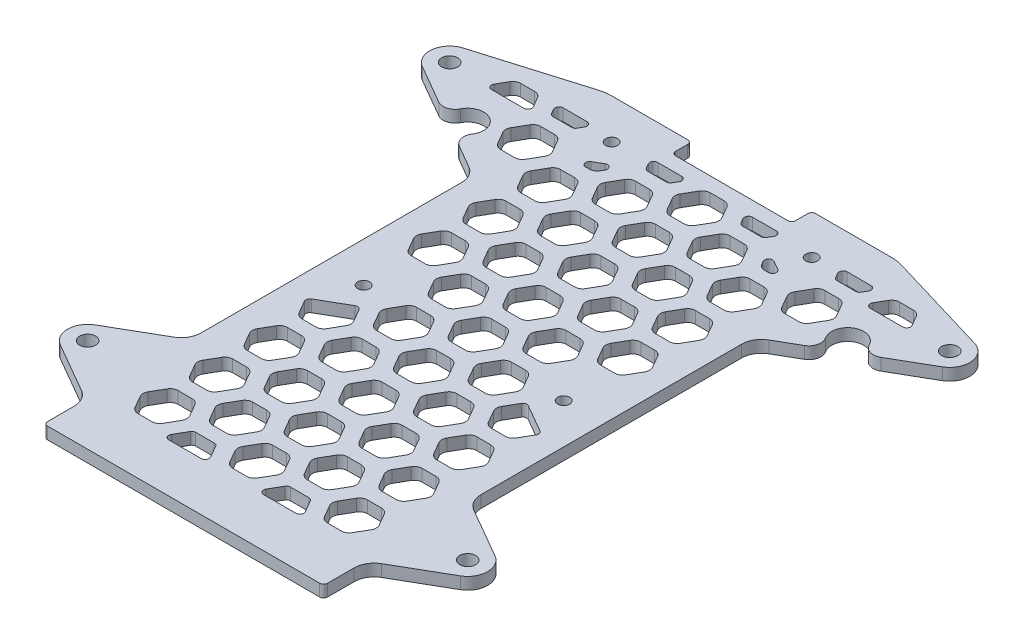
SolidWorks part; units mm, degrees
material "Thornel Mat VMA"
ref_plane "前视基准面" through (0, 0, 0) normal (0, 0, 1) x (1, 0, 0)
ref_plane "上视基准面" through (0, 0, 0) normal (0, 1, 0) x (1, 0, 0)
ref_plane "右视基准面" through (0, 0, 0) normal (1, 0, 0) x (0, 0, -1)
sketch "草图2" plane through (0, 0, 0) normal (0, 1, 0) x (1, 0, 0)
  line L0 (-43.1514, -19.9444) -> (-37.5, -23.2073)
  line L1 (35, -124.3771) -> (35, -132)
  line L3 (-47.5, -108.5) -> (-47.5, -13.5) construction
  line L6 (-37.8634, 9.5813) -> (-63.9317, 1.7906)
  line L7 (50, -112.8301) -> (37.5, -120.047)
  line L8 (37.5, -96.953) -> (50, -104.1699)
  line L11 (35, -27.5374) -> (35, -92.6229)
  line L14 (0, -55) -> (0, 55) construction
  line L16 (-35, 10) -> (35, 10)
  line L20 (43.1514, -19.9444) -> (37.5, -23.2073)
  line L23 (65, -7.3301) -> (55.2553, -12.9562)
  line L25 (-25, 0) -> (25, 0) construction
  line L26 (-25, 0) -> (-25, -62) construction
  line L27 (-25, -62) -> (25, -62) construction
  line L28 (25, 0) -> (25, -62) construction
  line L29 (-35, -124.3771) -> (-35, -132)
  line L30 (-35, -132) -> (35, -132)
  line L32 (-65, -7.3301) -> (-55.2553, -12.9562)
  line L33 (-35, -27.5374) -> (-35, -92.6229)
  line L34 (-37.5, -96.953) -> (-50, -104.1699)
  line L35 (-50, -112.8301) -> (-37.5, -120.047)
  line L36 (37.8634, 9.5813) -> (63.9317, 1.7906)
  arc A10 (-44.158, -15.6979) -> (-51.0745, -11.7047) centre (-47.5, -13.5) ccw
  circle A45 centre (-25, 0) radius 1.5
  circle A46 centre (-47.5, -38.5) radius 4 construction
  circle A47 centre (-62.5, -3) radius 2
  circle A49 centre (62.5, -3) radius 2
  circle A51 centre (47.5, -38.5) radius 4 construction
  circle A52 centre (25, 0) radius 1.5
  circle A53 centre (-25, -62) radius 1.5
  circle A54 centre (25, -62) radius 1.5
  arc A58 (-35, 10) -> (-37.8634, 9.5813) centre (-35, 0) ccw
  circle A59 centre (-47.5, -108.5) radius 2
  arc A60 (-50, -104.1699) -> (-50, -112.8301) centre (-47.5, -108.5) ccw
  arc A61 (-63.9317, 1.7906) -> (-65, -7.3301) centre (-62.5, -3) ccw
  arc A62 (-43.1514, -19.9444) -> (-44.158, -15.6979) centre (-41.6514, -17.3463) cw
  arc A63 (-51.0745, -11.7047) -> (-55.2553, -12.9562) centre (-53.7553, -10.3582) cw
  arc A64 (-35, -124.3771) -> (-37.5, -120.047) centre (-40, -124.3771) ccw
  arc A65 (-35, -92.6229) -> (-37.5, -96.953) centre (-40, -92.6229) cw
  arc A66 (-37.5, -23.2073) -> (-35, -27.5374) centre (-40, -27.5374) cw
  arc A67 (35, -124.3771) -> (37.5, -120.047) centre (40, -124.3771) cw
  circle A68 centre (47.5, -108.5) radius 2
  arc A69 (50, -104.1699) -> (50, -112.8301) centre (47.5, -108.5) cw
  arc A70 (35, -92.6229) -> (37.5, -96.953) centre (40, -92.6229) ccw
  arc A71 (37.5, -23.2073) -> (35, -27.5374) centre (40, -27.5374) ccw
  arc A72 (43.1514, -19.9444) -> (44.158, -15.6979) centre (41.6514, -17.3463) ccw
  arc A73 (44.158, -15.6979) -> (51.0745, -11.7047) centre (47.5, -13.5) cw
  arc A74 (51.0745, -11.7047) -> (55.2553, -12.9562) centre (53.7553, -10.3582) ccw
  arc A75 (63.9317, 1.7906) -> (65, -7.3301) centre (62.5, -3) cw
  arc A76 (35, 10) -> (37.8634, 9.5813) centre (35, 0) cw
  dimension "D3" = 10
  dimension "D4" = 25
  dimension "D7" = 5
  dimension "D8" = 125
  dimension "D9" = 13
  dimension "D10" = 3
  dimension "D11" = 10
  dimension "D6" = 4
  dimension "D19" = 120
  dimension "D20" = 3
  dimension "D21" = 62
  dimension "D22" = 50
  dimension "D23" = 5
  dimension "D13" = 15
  dimension "D14" = 10.5
  dimension "D12" = 70
  dimension "D15" = 10
  dimension "D16" = 70
  dimension "D17" = 120
  dimension "D18" = 120
  dimension "D5" = 8
extrude "凸台-拉伸1" add sketch "草图2" along normal blind 3
sketch "草图5" plane through (0, 3, 0) normal (0, 1, 0) x (1, 0, 0)
  line L0 (2.8868, -8.6667) -> (2.8868, -12.3333) construction
  line L26 (-20.7846, -12.3333) -> (-26.5581, -12.3333)
  line L29 (-26.5581, -12.3333) -> (-29.4449, -17.3333)
  line L34 (-29.4449, -17.3333) -> (-26.5581, -22.3333)
  line L35 (-26.5581, -22.3333) -> (-20.7846, -22.3333)
  line L47 (35, 10) -> (-35, 10) construction
  line L60 (-20.7846, -22.3333) -> (-17.8979, -17.3333)
  line L61 (-17.8979, -17.3333) -> (-20.7846, -12.3333)
  line L104 (0, 0) -> (0, 10) construction
  line L105 (-25, 0) -> (25, -62) construction
  line L109 (-11.8357, -10.5) -> (-11.8357, -24.1667) construction
  line L113 (-15, 10) -> (15, 10)
  line L114 (-15, 10) -> (-15, 5)
  line L115 (-15, 5) -> (15, 5)
  line L116 (15, 10) -> (15, 5)
  line L122 (2.8868, -12.3333) -> (-2.8868, -12.3333)
  line L123 (-2.8868, -12.3333) -> (-5.7735, -17.3333)
  line L124 (-5.7735, -17.3333) -> (-2.8868, -22.3333)
  line L125 (-2.8868, -22.3333) -> (2.8868, -22.3333)
  line L126 (2.8868, -22.3333) -> (5.7735, -17.3333)
  line L127 (5.7735, -17.3333) -> (2.8868, -12.3333)
  line L128 (-8.9489, -19.1667) -> (-14.7224, -19.1667)
  line L129 (-14.7224, -19.1667) -> (-17.6092, -24.1667)
  line L130 (-17.6092, -24.1667) -> (-14.7224, -29.1667)
  line L131 (-14.7224, -29.1667) -> (-8.9489, -29.1667)
  line L132 (-8.9489, -29.1667) -> (-6.0622, -24.1667)
  line L133 (-6.0622, -24.1667) -> (-8.9489, -19.1667)
  line L134 (-8.9489, -5.5) -> (-14.7224, -5.5)
  line L135 (-14.7224, -5.5) -> (-17.6092, -10.5)
  line L136 (-17.6092, -10.5) -> (-14.7224, -15.5)
  line L137 (-14.7224, -15.5) -> (-8.9489, -15.5)
  line L138 (-8.9489, -15.5) -> (-6.0622, -10.5)
  line L139 (-6.0622, -10.5) -> (-8.9489, -5.5)
  line L140 (-11.8357, -24.1667) -> (0, -31) construction
  line L141 (0, -31) -> (0, -17.3333) construction
  line L142 (0, -17.3333) -> (-11.8357, -24.1667) construction
  line L143 (0, -3.6667) -> (0, -17.3333) construction
  line L144 (2.8868, 1.3333) -> (-2.8868, 1.3333)
  line L145 (-2.8868, 1.3333) -> (-5.7735, -3.6667)
  line L146 (-5.7735, -3.6667) -> (-2.8868, -8.6667)
  line L147 (-2.8868, -8.6667) -> (2.8868, -8.6667)
  line L148 (2.8868, -8.6667) -> (5.7735, -3.6667)
  line L149 (5.7735, -3.6667) -> (2.8868, 1.3333)
  line L151 (2.8868, 1.3333) -> (2.8868, 5) construction
  line L155 (-32.6203, -5.5) -> (-38.3938, -5.5)
  line L156 (-38.3938, -5.5) -> (-41.2805, -10.5)
  line L157 (-41.2805, -10.5) -> (-38.3938, -15.5)
  line L158 (-38.3938, -15.5) -> (-32.6203, -15.5)
  line L159 (-32.6203, -15.5) -> (-29.7335, -10.5)
  line L160 (-29.7335, -10.5) -> (-32.6203, -5.5)
  line L164 (-26.5581, -8.6667) -> (-20.7846, -8.6667)
  line L165 (-20.7846, -8.6667) -> (-17.8979, -3.6667)
  line L185 (-44.456, 1.3333) -> (-50.2295, 1.3333)
  line L186 (-50.2295, 1.3333) -> (-53.1162, -3.6667)
  line L190 (-41.5692, -3.6667) -> (-44.456, 1.3333)
  line L191 (-20.7846, -39.6667) -> (-26.5581, -39.6667)
  line L192 (-26.5581, -39.6667) -> (-29.4449, -44.6667)
  line L193 (-29.4449, -44.6667) -> (-26.5581, -49.6667)
  line L194 (-26.5581, -49.6667) -> (-20.7846, -49.6667)
  line L195 (-20.7846, -49.6667) -> (-17.8979, -44.6667)
  line L196 (-17.8979, -44.6667) -> (-20.7846, -39.6667)
  line L209 (-20.7846, -26) -> (-26.5581, -26)
  line L210 (-26.5581, -26) -> (-29.4449, -31)
  line L211 (-29.4449, -31) -> (-26.5581, -36)
  line L212 (-26.5581, -36) -> (-20.7846, -36)
  line L213 (-20.7846, -36) -> (-17.8979, -31)
  line L214 (-17.8979, -31) -> (-20.7846, -26)
  line L241 (-29.4449, -72) -> (-26.5581, -77)
  line L242 (-26.5581, -77) -> (-20.7846, -77)
  line L243 (-20.7846, -77) -> (-17.8979, -72)
  line L244 (-17.8979, -72) -> (-20.7846, -67)
  line L287 (-20.7846, -94.3333) -> (-26.5581, -94.3333)
  line L288 (-26.5581, -94.3333) -> (-29.4449, -99.3333)
  line L289 (-29.4449, -99.3333) -> (-26.5581, -104.3333)
  line L290 (-26.5581, -104.3333) -> (-20.7846, -104.3333)
  line L291 (-20.7846, -104.3333) -> (-17.8979, -99.3333)
  line L292 (-17.8979, -99.3333) -> (-20.7846, -94.3333)
  line L305 (-20.7846, -80.6667) -> (-26.5581, -80.6667)
  line L306 (-26.5581, -80.6667) -> (-29.4449, -85.6667)
  line L307 (-29.4449, -85.6667) -> (-26.5581, -90.6667)
  line L308 (-26.5581, -90.6667) -> (-20.7846, -90.6667)
  line L309 (-20.7846, -90.6667) -> (-17.8979, -85.6667)
  line L310 (-17.8979, -85.6667) -> (-20.7846, -80.6667)
  line L353 (-20.7846, -108) -> (-26.5581, -108)
  line L354 (-26.5581, -108) -> (-29.4449, -113)
  line L355 (-29.4449, -113) -> (-26.5581, -118)
  line L356 (-26.5581, -118) -> (-20.7846, -118)
  line L357 (-20.7846, -118) -> (-17.8979, -113)
  line L358 (-17.8979, -113) -> (-20.7846, -108)
  line L431 (2.8868, -39.6667) -> (-2.8868, -39.6667)
  line L432 (-2.8868, -39.6667) -> (-5.7735, -44.6667)
  line L433 (-5.7735, -44.6667) -> (-2.8868, -49.6667)
  line L434 (-2.8868, -49.6667) -> (2.8868, -49.6667)
  line L435 (2.8868, -49.6667) -> (5.7735, -44.6667)
  line L436 (5.7735, -44.6667) -> (2.8868, -39.6667)
  line L437 (-8.9489, -46.5) -> (-14.7224, -46.5)
  line L438 (-14.7224, -46.5) -> (-17.6092, -51.5)
  line L439 (-17.6092, -51.5) -> (-14.7224, -56.5)
  line L440 (-14.7224, -56.5) -> (-8.9489, -56.5)
  line L441 (-8.9489, -56.5) -> (-6.0622, -51.5)
  line L442 (-6.0622, -51.5) -> (-8.9489, -46.5)
  line L443 (-8.9489, -32.8333) -> (-14.7224, -32.8333)
  line L444 (-14.7224, -32.8333) -> (-17.6092, -37.8333)
  line L445 (-17.6092, -37.8333) -> (-14.7224, -42.8333)
  line L446 (-14.7224, -42.8333) -> (-8.9489, -42.8333)
  line L447 (-8.9489, -42.8333) -> (-6.0622, -37.8333)
  line L448 (-6.0622, -37.8333) -> (-8.9489, -32.8333)
  line L449 (2.8868, -26) -> (-2.8868, -26)
  line L450 (-2.8868, -26) -> (-5.7735, -31)
  line L451 (-5.7735, -31) -> (-2.8868, -36)
  line L452 (-2.8868, -36) -> (2.8868, -36)
  line L453 (2.8868, -36) -> (5.7735, -31)
  line L454 (5.7735, -31) -> (2.8868, -26)
  line L455 (2.8868, -67) -> (-2.8868, -67)
  line L456 (-2.8868, -67) -> (-5.7735, -72)
  line L457 (-5.7735, -72) -> (-2.8868, -77)
  line L458 (-2.8868, -77) -> (2.8868, -77)
  line L459 (2.8868, -77) -> (5.7735, -72)
  line L460 (5.7735, -72) -> (2.8868, -67)
  line L461 (-8.9489, -73.8333) -> (-14.7224, -73.8333)
  line L462 (-14.7224, -73.8333) -> (-17.6092, -78.8333)
  line L463 (-17.6092, -78.8333) -> (-14.7224, -83.8333)
  line L464 (-14.7224, -83.8333) -> (-8.9489, -83.8333)
  line L465 (-8.9489, -83.8333) -> (-6.0622, -78.8333)
  line L466 (-6.0622, -78.8333) -> (-8.9489, -73.8333)
  line L467 (-8.9489, -60.1667) -> (-14.7224, -60.1667)
  line L468 (-14.7224, -60.1667) -> (-17.6092, -65.1667)
  line L469 (-17.6092, -65.1667) -> (-14.7224, -70.1667)
  line L470 (-14.7224, -70.1667) -> (-8.9489, -70.1667)
  line L471 (-8.9489, -70.1667) -> (-6.0622, -65.1667)
  line L472 (-6.0622, -65.1667) -> (-8.9489, -60.1667)
  line L473 (2.8868, -53.3333) -> (-2.8868, -53.3333)
  line L474 (-2.8868, -53.3333) -> (-5.7735, -58.3333)
  line L475 (-5.7735, -58.3333) -> (-2.8868, -63.3333)
  line L476 (-2.8868, -63.3333) -> (2.8868, -63.3333)
  line L477 (2.8868, -63.3333) -> (5.7735, -58.3333)
  line L478 (5.7735, -58.3333) -> (2.8868, -53.3333)
  line L479 (2.8868, -94.3333) -> (-2.8868, -94.3333)
  line L480 (-2.8868, -94.3333) -> (-5.7735, -99.3333)
  line L481 (-5.7735, -99.3333) -> (-2.8868, -104.3333)
  line L482 (-2.8868, -104.3333) -> (2.8868, -104.3333)
  line L483 (2.8868, -104.3333) -> (5.7735, -99.3333)
  line L484 (5.7735, -99.3333) -> (2.8868, -94.3333)
  line L485 (-8.9489, -101.1667) -> (-14.7224, -101.1667)
  line L486 (-14.7224, -101.1667) -> (-17.6092, -106.1667)
  line L487 (-17.6092, -106.1667) -> (-14.7224, -111.1667)
  line L488 (-14.7224, -111.1667) -> (-8.9489, -111.1667)
  line L489 (-8.9489, -111.1667) -> (-6.0622, -106.1667)
  line L490 (-6.0622, -106.1667) -> (-8.9489, -101.1667)
  line L491 (-8.9489, -87.5) -> (-14.7224, -87.5)
  line L492 (-14.7224, -87.5) -> (-17.6092, -92.5)
  line L493 (-17.6092, -92.5) -> (-14.7224, -97.5)
  line L494 (-14.7224, -97.5) -> (-8.9489, -97.5)
  line L495 (-8.9489, -97.5) -> (-6.0622, -92.5)
  line L496 (-6.0622, -92.5) -> (-8.9489, -87.5)
  line L497 (2.8868, -80.6667) -> (-2.8868, -80.6667)
  line L498 (-2.8868, -80.6667) -> (-5.7735, -85.6667)
  line L499 (-5.7735, -85.6667) -> (-2.8868, -90.6667)
  line L500 (-2.8868, -90.6667) -> (2.8868, -90.6667)
  line L501 (2.8868, -90.6667) -> (5.7735, -85.6667)
  line L502 (5.7735, -85.6667) -> (2.8868, -80.6667)
  line L515 (-8.9489, -114.8333) -> (-14.7224, -114.8333)
  line L516 (-14.7224, -114.8333) -> (-17.6092, -119.8333)
  line L520 (-6.0622, -119.8333) -> (-8.9489, -114.8333)
  line L521 (2.8868, -108) -> (-2.8868, -108)
  line L522 (-2.8868, -108) -> (-5.7735, -113)
  line L523 (-5.7735, -113) -> (-2.8868, -118)
  line L524 (-2.8868, -118) -> (2.8868, -118)
  line L525 (2.8868, -118) -> (5.7735, -113)
  line L526 (5.7735, -113) -> (2.8868, -108)
  line L551 (-11.8357, -10.5) -> (-23.6714, -17.3333) construction
  line L552 (-23.6714, -17.3333) -> (-11.8357, -24.1667) construction
  line L553 (-17.8979, -3.6667) -> (-26.5581, -8.6667)
  line L554 (-62.0652, -56.5) -> (-56.2917, -56.5) [skipped]
  line L555 (-44.456, -67) -> (-50.2295, -67) [skipped]
  line L556 (-50.2295, -67) -> (-53.1162, -72) [skipped]
  line L557 (-53.1162, -72) -> (-50.2295, -77) [skipped]
  line L558 (-50.2295, -77) -> (-44.456, -77) [skipped]
  line L559 (-44.456, -77) -> (-41.5692, -72) [skipped]
  line L560 (-41.5692, -72) -> (-44.456, -67) [skipped]
  line L561 (-56.2917, -73.8333) -> (-62.0652, -73.8333) [skipped]
  line L562 (-62.0652, -73.8333) -> (-64.9519, -78.8333) [skipped]
  line L563 (-64.9519, -78.8333) -> (-62.0652, -83.8333) [skipped]
  line L564 (-62.0652, -83.8333) -> (-56.2917, -83.8333) [skipped]
  line L565 (-56.2917, -83.8333) -> (-53.4049, -78.8333) [skipped]
  line L566 (-53.4049, -78.8333) -> (-56.2917, -73.8333) [skipped]
  line L567 (-56.2917, -60.1667) -> (-62.0652, -60.1667) [skipped]
  line L568 (-62.0652, -60.1667) -> (-64.9519, -65.1667) [skipped]
  line L569 (-64.9519, -65.1667) -> (-62.0652, -70.1667) [skipped]
  line L570 (-62.0652, -70.1667) -> (-56.2917, -70.1667) [skipped]
  line L571 (-56.2917, -70.1667) -> (-53.4049, -65.1667) [skipped]
  line L572 (-53.4049, -65.1667) -> (-56.2917, -60.1667) [skipped]
  line L573 (-53.1162, -58.3333) -> (-50.2295, -63.3333) [skipped]
  line L574 (-50.2295, -63.3333) -> (-44.456, -63.3333) [skipped]
  line L575 (-44.456, -63.3333) -> (-41.5692, -58.3333) [skipped]
  line L576 (-44.456, -94.3333) -> (-50.2295, -94.3333) [skipped]
  line L577 (-50.2295, -94.3333) -> (-53.1162, -99.3333) [skipped]
  line L578 (-53.1162, -99.3333) -> (-50.2295, -104.3333) [skipped]
  line L579 (-50.2295, -104.3333) -> (-44.456, -104.3333) [skipped]
  line L580 (-44.456, -104.3333) -> (-41.5692, -99.3333) [skipped]
  line L581 (-41.5692, -99.3333) -> (-44.456, -94.3333) [skipped]
  line L582 (-56.2917, -101.1667) -> (-62.0652, -101.1667) [skipped]
  line L583 (-62.0652, -101.1667) -> (-64.9519, -106.1667) [skipped]
  line L584 (-64.9519, -106.1667) -> (-62.0652, -111.1667) [skipped]
  line L585 (-62.0652, -111.1667) -> (-56.2917, -111.1667) [skipped]
  line L586 (-56.2917, -111.1667) -> (-53.4049, -106.1667) [skipped]
  line L587 (-53.4049, -106.1667) -> (-56.2917, -101.1667) [skipped]
  line L588 (-56.2917, -87.5) -> (-62.0652, -87.5) [skipped]
  line L589 (-62.0652, -87.5) -> (-64.9519, -92.5) [skipped]
  line L590 (-64.9519, -92.5) -> (-62.0652, -97.5) [skipped]
  line L591 (-62.0652, -97.5) -> (-56.2917, -97.5) [skipped]
  line L592 (-56.2917, -97.5) -> (-53.4049, -92.5) [skipped]
  line L593 (-53.4049, -92.5) -> (-56.2917, -87.5) [skipped]
  line L594 (-44.456, -80.6667) -> (-50.2295, -80.6667) [skipped]
  line L595 (-50.2295, -80.6667) -> (-53.1162, -85.6667) [skipped]
  line L596 (-53.1162, -85.6667) -> (-50.2295, -90.6667) [skipped]
  line L597 (-50.2295, -90.6667) -> (-44.456, -90.6667) [skipped]
  line L598 (-44.456, -90.6667) -> (-41.5692, -85.6667) [skipped]
  line L599 (-41.5692, -85.6667) -> (-44.456, -80.6667) [skipped]
  line L600 (-44.456, -121.6667) -> (-50.2295, -121.6667) [skipped]
  line L601 (-50.2295, -121.6667) -> (-53.1162, -126.6667) [skipped]
  line L602 (-53.1162, -126.6667) -> (-50.2295, -131.6667) [skipped]
  line L603 (-50.2295, -131.6667) -> (-44.456, -131.6667) [skipped]
  line L604 (-44.456, -131.6667) -> (-41.5692, -126.6667) [skipped]
  line L605 (-41.5692, -126.6667) -> (-44.456, -121.6667) [skipped]
  line L606 (-56.2917, -128.5) -> (-62.0652, -128.5) [skipped]
  line L607 (-62.0652, -128.5) -> (-64.9519, -133.5) [skipped]
  line L608 (-64.9519, -133.5) -> (-62.0652, -138.5) [skipped]
  line L609 (-62.0652, -138.5) -> (-56.2917, -138.5) [skipped]
  line L610 (-56.2917, -138.5) -> (-53.4049, -133.5) [skipped]
  line L611 (-53.4049, -133.5) -> (-56.2917, -128.5) [skipped]
  line L612 (-56.2917, -114.8333) -> (-62.0652, -114.8333) [skipped]
  line L613 (-62.0652, -114.8333) -> (-64.9519, -119.8333) [skipped]
  line L614 (-64.9519, -119.8333) -> (-62.0652, -124.8333) [skipped]
  line L615 (-62.0652, -124.8333) -> (-56.2917, -124.8333) [skipped]
  line L616 (-56.2917, -124.8333) -> (-53.4049, -119.8333) [skipped]
  line L617 (-53.4049, -119.8333) -> (-56.2917, -114.8333) [skipped]
  line L618 (-44.456, -108) -> (-50.2295, -108) [skipped]
  line L619 (-50.2295, -108) -> (-53.1162, -113) [skipped]
  line L620 (-53.1162, -113) -> (-50.2295, -118) [skipped]
  line L621 (-50.2295, -118) -> (-44.456, -118) [skipped]
  line L622 (-44.456, -118) -> (-41.5692, -113) [skipped]
  line L623 (-41.5692, -113) -> (-44.456, -108) [skipped]
  line L624 (-44.456, -149) -> (-50.2295, -149) [skipped]
  line L625 (-50.2295, -149) -> (-53.1162, -154) [skipped]
  line L626 (-53.1162, -154) -> (-50.2295, -159) [skipped]
  line L627 (-50.2295, -159) -> (-44.456, -159) [skipped]
  line L628 (-44.456, -159) -> (-41.5692, -154) [skipped]
  line L629 (-41.5692, -154) -> (-44.456, -149) [skipped]
  line L630 (-56.2917, -155.8333) -> (-62.0652, -155.8333) [skipped]
  line L631 (-62.0652, -155.8333) -> (-64.9519, -160.8333) [skipped]
  line L632 (-64.9519, -160.8333) -> (-62.0652, -165.8333) [skipped]
  line L633 (-62.0652, -165.8333) -> (-56.2917, -165.8333) [skipped]
  line L634 (-56.2917, -165.8333) -> (-53.4049, -160.8333) [skipped]
  line L635 (-53.4049, -160.8333) -> (-56.2917, -155.8333) [skipped]
  line L636 (-56.2917, -142.1667) -> (-62.0652, -142.1667) [skipped]
  line L637 (-62.0652, -142.1667) -> (-64.9519, -147.1667) [skipped]
  line L638 (-64.9519, -147.1667) -> (-62.0652, -152.1667) [skipped]
  line L639 (-62.0652, -152.1667) -> (-56.2917, -152.1667) [skipped]
  line L640 (-56.2917, -152.1667) -> (-53.4049, -147.1667) [skipped]
  line L641 (-53.4049, -147.1667) -> (-56.2917, -142.1667) [skipped]
  line L642 (-44.456, -135.3333) -> (-50.2295, -135.3333) [skipped]
  line L643 (-50.2295, -135.3333) -> (-53.1162, -140.3333) [skipped]
  line L644 (-53.1162, -140.3333) -> (-50.2295, -145.3333) [skipped]
  line L645 (-50.2295, -145.3333) -> (-44.456, -145.3333) [skipped]
  line L646 (-44.456, -145.3333) -> (-41.5692, -140.3333) [skipped]
  line L647 (-41.5692, -140.3333) -> (-44.456, -135.3333) [skipped]
  line L648 (-44.456, -12.3333) -> (-50.2295, -12.3333) [skipped]
  line L649 (-50.2295, -12.3333) -> (-53.1162, -17.3333) [skipped]
  line L650 (-53.1162, -17.3333) -> (-50.2295, -22.3333) [skipped]
  line L651 (-50.2295, -22.3333) -> (-44.456, -22.3333) [skipped]
  line L652 (-44.456, -22.3333) -> (-41.5692, -17.3333) [skipped]
  line L653 (-41.5692, -17.3333) -> (-44.456, -12.3333) [skipped]
  line L654 (-56.2917, -19.1667) -> (-62.0652, -19.1667) [skipped]
  line L655 (-62.0652, -19.1667) -> (-64.9519, -24.1667) [skipped]
  line L656 (-64.9519, -24.1667) -> (-62.0652, -29.1667) [skipped]
  line L657 (-62.0652, -29.1667) -> (-56.2917, -29.1667) [skipped]
  line L658 (-56.2917, -29.1667) -> (-53.4049, -24.1667) [skipped]
  line L659 (-53.4049, -24.1667) -> (-56.2917, -19.1667) [skipped]
  line L660 (-64.9519, -10.5) -> (-62.0652, -15.5) [skipped]
  line L661 (-62.0652, -15.5) -> (-56.2917, -15.5) [skipped]
  line L662 (-56.2917, -15.5) -> (-53.4049, -10.5) [skipped]
  line L663 (-44.456, -39.6667) -> (-50.2295, -39.6667) [skipped]
  line L664 (-50.2295, -39.6667) -> (-53.1162, -44.6667) [skipped]
  line L665 (-53.1162, -44.6667) -> (-50.2295, -49.6667) [skipped]
  line L666 (-50.2295, -49.6667) -> (-44.456, -49.6667) [skipped]
  line L667 (-44.456, -49.6667) -> (-41.5692, -44.6667) [skipped]
  line L668 (-41.5692, -44.6667) -> (-44.456, -39.6667) [skipped]
  line L669 (-56.2917, -46.5) -> (-62.0652, -46.5) [skipped]
  line L670 (-62.0652, -46.5) -> (-64.9519, -51.5) [skipped]
  line L671 (-64.9519, -51.5) -> (-62.0652, -56.5) [skipped]
  line L672 (-56.2917, -56.5) -> (-53.4049, -51.5) [skipped]
  line L673 (-53.4049, -51.5) -> (-56.2917, -46.5) [skipped]
  line L674 (-56.2917, -32.8333) -> (-62.0652, -32.8333) [skipped]
  line L675 (-62.0652, -32.8333) -> (-64.9519, -37.8333) [skipped]
  line L676 (-64.9519, -37.8333) -> (-62.0652, -42.8333) [skipped]
  line L677 (-62.0652, -42.8333) -> (-56.2917, -42.8333) [skipped]
  line L678 (-56.2917, -42.8333) -> (-53.4049, -37.8333) [skipped]
  line L679 (-53.4049, -37.8333) -> (-56.2917, -32.8333) [skipped]
  line L680 (-44.456, -26) -> (-50.2295, -26) [skipped]
  line L681 (-50.2295, -26) -> (-53.1162, -31) [skipped]
  line L682 (-53.1162, -31) -> (-50.2295, -36) [skipped]
  line L683 (-50.2295, -36) -> (-44.456, -36) [skipped]
  line L684 (-44.456, -36) -> (-41.5692, -31) [skipped]
  line L685 (-41.5692, -31) -> (-44.456, -26) [skipped]
  line L686 (-44.456, -53.3333) -> (-50.2295, -53.3333) [skipped]
  line L687 (-50.2295, -53.3333) -> (-53.1162, -58.3333) [skipped]
  line L688 (-41.5692, -58.3333) -> (-44.456, -53.3333) [skipped]
  line L689 (-56.2917, -5.5) -> (-62.0652, -5.5) [skipped]
  line L690 (-62.0652, -5.5) -> (-64.9519, -10.5) [skipped]
  line L691 (-53.4049, -10.5) -> (-56.2917, -5.5) [skipped]
  line L692 (-16.5507, 1.3333) -> (-14.7224, -1.8333)
  line L693 (-14.7224, -1.8333) -> (-8.9489, -1.8333)
  line L694 (-8.9489, -1.8333) -> (-7.1207, 1.3333)
  line L695 (-7.1207, 1.3333) -> (-16.5507, 1.3333)
  line L696 (-8.9489, -1.8333) -> (-8.9489, -5.5) construction
  line L697 (-38.3938, -5.5) -> (-38.3938, -1.8333) construction
  line L698 (-20.7846, 1.3333) -> (-26.5581, 1.3333) [skipped]
  line L699 (-26.5581, 1.3333) -> (-29.4449, -3.6667) [skipped]
  line L700 (-40.2221, 1.3333) -> (-30.792, 1.3333)
  line L701 (-40.2221, 1.3333) -> (-38.3938, -1.8333)
  line L702 (-38.3938, -1.8333) -> (-32.6203, -1.8333)
  line L703 (-30.792, 1.3333) -> (-32.6203, -1.8333)
  line L705 (-38.3938, -19.1667) -> (-41.2805, -24.1667) [skipped]
  line L706 (-41.2805, -24.1667) -> (-38.3938, -29.1667) [skipped]
  line L707 (-38.3938, -29.1667) -> (-32.6203, -29.1667) [skipped]
  line L708 (-32.6203, -46.5) -> (-38.3938, -46.5) [skipped]
  line L709 (-38.3938, -46.5) -> (-41.2805, -51.5) [skipped]
  line L710 (-41.2805, -51.5) -> (-38.3938, -56.5) [skipped]
  line L711 (-38.3938, -56.5) -> (-32.6203, -56.5) [skipped]
  line L712 (-32.6203, -32.8333) -> (-38.3938, -32.8333) [skipped]
  line L713 (-38.3938, -32.8333) -> (-41.2805, -37.8333) [skipped]
  line L714 (-41.2805, -37.8333) -> (-38.3938, -42.8333) [skipped]
  line L715 (-38.3938, -42.8333) -> (-32.6203, -42.8333) [skipped]
  line L716 (-32.6203, -73.8333) -> (-38.3938, -73.8333) [skipped]
  line L717 (-38.3938, -73.8333) -> (-41.2805, -78.8333) [skipped]
  line L718 (-41.2805, -78.8333) -> (-38.3938, -83.8333) [skipped]
  line L719 (-38.3938, -83.8333) -> (-32.6203, -83.8333) [skipped]
  line L720 (-32.6203, -60.1667) -> (-38.3938, -60.1667) [skipped]
  line L721 (-38.3938, -60.1667) -> (-41.2805, -65.1667) [skipped]
  line L722 (-41.2805, -65.1667) -> (-38.3938, -70.1667) [skipped]
  line L723 (-38.3938, -70.1667) -> (-32.6203, -70.1667) [skipped]
  line L724 (-32.6203, -101.1667) -> (-38.3938, -101.1667) [skipped]
  line L725 (-38.3938, -101.1667) -> (-41.2805, -106.1667) [skipped]
  line L726 (-41.2805, -106.1667) -> (-38.3938, -111.1667) [skipped]
  line L727 (-38.3938, -111.1667) -> (-32.6203, -111.1667) [skipped]
  line L728 (-32.6203, -87.5) -> (-38.3938, -87.5) [skipped]
  line L729 (-38.3938, -87.5) -> (-41.2805, -92.5) [skipped]
  line L730 (-41.2805, -92.5) -> (-38.3938, -97.5) [skipped]
  line L731 (-38.3938, -97.5) -> (-32.6203, -97.5) [skipped]
  line L732 (-32.6203, -128.5) -> (-38.3938, -128.5) [skipped]
  line L733 (-38.3938, -128.5) -> (-41.2805, -133.5) [skipped]
  line L734 (-41.2805, -133.5) -> (-38.3938, -138.5) [skipped]
  line L735 (-38.3938, -138.5) -> (-32.6203, -138.5) [skipped]
  line L736 (-32.6203, -114.8333) -> (-38.3938, -114.8333) [skipped]
  line L737 (-38.3938, -114.8333) -> (-41.2805, -119.8333) [skipped]
  line L738 (-41.2805, -119.8333) -> (-38.3938, -124.8333) [skipped]
  line L739 (-38.3938, -124.8333) -> (-32.6203, -124.8333) [skipped]
  line L740 (-32.6203, -155.8333) -> (-38.3938, -155.8333) [skipped]
  line L741 (-38.3938, -155.8333) -> (-41.2805, -160.8333) [skipped]
  line L742 (-41.2805, -160.8333) -> (-38.3938, -165.8333) [skipped]
  line L743 (-38.3938, -165.8333) -> (-32.6203, -165.8333) [skipped]
  line L744 (-32.6203, -142.1667) -> (-38.3938, -142.1667) [skipped]
  line L745 (-38.3938, -142.1667) -> (-41.2805, -147.1667) [skipped]
  line L746 (-41.2805, -147.1667) -> (-38.3938, -152.1667) [skipped]
  line L747 (-38.3938, -152.1667) -> (-32.6203, -152.1667) [skipped]
  line L748 (-20.7846, -149) -> (-26.5581, -149) [skipped]
  line L749 (-26.5581, -149) -> (-29.4449, -154) [skipped]
  line L750 (-29.4449, -154) -> (-26.5581, -159) [skipped]
  line L751 (-26.5581, -159) -> (-20.7846, -159) [skipped]
  line L752 (-20.7846, -159) -> (-17.8979, -154) [skipped]
  line L753 (-17.8979, -154) -> (-20.7846, -149) [skipped]
  line L754 (-32.6203, -165.8333) -> (-29.7335, -160.8333) [skipped]
  line L755 (-29.7335, -160.8333) -> (-32.6203, -155.8333) [skipped]
  line L756 (-32.6203, -152.1667) -> (-29.7335, -147.1667) [skipped]
  line L757 (-29.7335, -147.1667) -> (-32.6203, -142.1667) [skipped]
  line L758 (-29.4449, -140.3333) -> (-26.5581, -145.3333) [skipped]
  line L759 (-26.5581, -145.3333) -> (-20.7846, -145.3333) [skipped]
  line L760 (-20.7846, -145.3333) -> (-17.8979, -140.3333) [skipped]
  line L761 (2.8868, -149) -> (-2.8868, -149) [skipped]
  line L762 (-2.8868, -149) -> (-5.7735, -154) [skipped]
  line L763 (-5.7735, -154) -> (-2.8868, -159) [skipped]
  line L764 (-2.8868, -159) -> (2.8868, -159) [skipped]
  line L765 (2.8868, -159) -> (5.7735, -154) [skipped]
  line L766 (5.7735, -154) -> (2.8868, -149) [skipped]
  line L767 (-8.9489, -155.8333) -> (-14.7224, -155.8333) [skipped]
  line L768 (-14.7224, -155.8333) -> (-17.6092, -160.8333) [skipped]
  line L769 (-17.6092, -160.8333) -> (-14.7224, -165.8333) [skipped]
  line L770 (-14.7224, -165.8333) -> (-8.9489, -165.8333) [skipped]
  line L771 (-8.9489, -165.8333) -> (-6.0622, -160.8333) [skipped]
  line L772 (-6.0622, -160.8333) -> (-8.9489, -155.8333) [skipped]
  line L773 (-14.7224, -142.1667) -> (-17.6092, -147.1667) [skipped]
  line L774 (-17.6092, -147.1667) -> (-14.7224, -152.1667) [skipped]
  line L775 (-14.7224, -152.1667) -> (-8.9489, -152.1667) [skipped]
  line L776 (-8.9489, -152.1667) -> (-6.0622, -147.1667) [skipped]
  line L777 (-6.0622, -147.1667) -> (-8.9489, -142.1667) [skipped]
  line L778 (-5.7735, -140.3333) -> (-2.8868, -145.3333) [skipped]
  line L779 (-2.8868, -145.3333) -> (2.8868, -145.3333) [skipped]
  line L780 (2.8868, -145.3333) -> (5.7735, -140.3333) [skipped]
  line L781 (-8.9489, -142.1667) -> (-14.7224, -142.1667) [skipped]
  line L792 (-29.4449, -72) -> (-20.7846, -67)
  line L793 (-17.6092, -119.8333) -> (-6.0622, -119.8333)
  line L795 (-53.1162, -3.6667) -> (-41.5692, -3.6667)
  line L796 (-26.5581, -63.3333) -> (-20.7846, -63.3333) [skipped]
  line L797 (-29.4449, -58.3333) -> (-26.5581, -63.3333) [skipped]
  line L798 (-20.7846, -67) -> (-26.5581, -67) [skipped]
  line L799 (-26.5581, -67) -> (-29.4449, -72) [skipped]
  line L800 (-32.6203, -70.1667) -> (-29.7335, -65.1667) [skipped]
  line L801 (-29.7335, -65.1667) -> (-32.6203, -60.1667) [skipped]
  line L802 (-17.8979, -3.6667) -> (-20.7846, 1.3333) [skipped]
  line L803 (-29.4449, -3.6667) -> (-26.5581, -8.6667) [skipped]
  line L804 (-20.7846, -53.3333) -> (-26.5581, -53.3333) [skipped]
  line L805 (-26.5581, -53.3333) -> (-29.4449, -58.3333) [skipped]
  line L806 (-17.8979, -58.3333) -> (-20.7846, -53.3333) [skipped]
  line L807 (-20.7846, -63.3333) -> (-17.8979, -58.3333) [skipped]
  line L808 (-2.8868, -121.6667) -> (-5.7735, -126.6667) [skipped]
  line L809 (-5.7735, -126.6667) -> (-2.8868, -131.6667) [skipped]
  line L810 (-2.8868, -131.6667) -> (2.8868, -131.6667) [skipped]
  line L811 (2.8868, -131.6667) -> (5.7735, -126.6667) [skipped]
  line L812 (5.7735, -126.6667) -> (2.8868, -121.6667) [skipped]
  line L813 (2.8868, -135.3333) -> (-2.8868, -135.3333) [skipped]
  line L814 (-2.8868, -135.3333) -> (-5.7735, -140.3333) [skipped]
  line L815 (5.7735, -140.3333) -> (2.8868, -135.3333) [skipped]
  line L816 (2.8868, -121.6667) -> (-2.8868, -121.6667) [skipped]
  line L817 (-32.6203, -19.1667) -> (-38.3938, -19.1667) [skipped]
  line L818 (-32.6203, -29.1667) -> (-29.7335, -24.1667) [skipped]
  line L819 (-29.7335, -24.1667) -> (-32.6203, -19.1667) [skipped]
  line L820 (-32.6203, -56.5) -> (-29.7335, -51.5) [skipped]
  line L821 (-29.7335, -51.5) -> (-32.6203, -46.5) [skipped]
  line L822 (-32.6203, -42.8333) -> (-29.7335, -37.8333) [skipped]
  line L823 (-29.7335, -37.8333) -> (-32.6203, -32.8333) [skipped]
  line L824 (-32.6203, -83.8333) -> (-29.7335, -78.8333) [skipped]
  line L825 (-29.7335, -78.8333) -> (-32.6203, -73.8333) [skipped]
  line L826 (-32.6203, -97.5) -> (-29.7335, -92.5) [skipped]
  line L827 (-29.7335, -92.5) -> (-32.6203, -87.5) [skipped]
  line L828 (-32.6203, -111.1667) -> (-29.7335, -106.1667) [skipped]
  line L829 (-29.7335, -106.1667) -> (-32.6203, -101.1667) [skipped]
  line L830 (-32.6203, -138.5) -> (-29.7335, -133.5) [skipped]
  line L831 (-29.7335, -133.5) -> (-32.6203, -128.5) [skipped]
  line L832 (-32.6203, -124.8333) -> (-29.7335, -119.8333) [skipped]
  line L833 (-29.7335, -119.8333) -> (-32.6203, -114.8333) [skipped]
  line L834 (-26.5581, -121.6667) -> (-29.4449, -126.6667) [skipped]
  line L835 (-29.4449, -126.6667) -> (-26.5581, -131.6667) [skipped]
  line L836 (-26.5581, -131.6667) -> (-20.7846, -131.6667) [skipped]
  line L837 (-20.7846, -131.6667) -> (-17.8979, -126.6667) [skipped]
  line L838 (-17.8979, -126.6667) -> (-20.7846, -121.6667) [skipped]
  line L839 (-20.7846, -135.3333) -> (-26.5581, -135.3333) [skipped]
  line L840 (-26.5581, -135.3333) -> (-29.4449, -140.3333) [skipped]
  line L841 (-17.8979, -140.3333) -> (-20.7846, -135.3333) [skipped]
  line L842 (-8.9489, -128.5) -> (-14.7224, -128.5) [skipped]
  line L843 (-14.7224, -128.5) -> (-17.6092, -133.5) [skipped]
  line L844 (-17.6092, -133.5) -> (-14.7224, -138.5) [skipped]
  line L845 (-14.7224, -138.5) -> (-8.9489, -138.5) [skipped]
  line L846 (-8.9489, -138.5) -> (-6.0622, -133.5) [skipped]
  line L847 (-6.0622, -133.5) -> (-8.9489, -128.5) [skipped]
  line L848 (-20.7846, -121.6667) -> (-26.5581, -121.6667) [skipped]
  line L849 (-17.6092, -119.8333) -> (-14.7224, -124.8333) [skipped]
  line L850 (-14.7224, -124.8333) -> (-8.9489, -124.8333) [skipped]
  line L851 (-8.9489, -124.8333) -> (-6.0622, -119.8333) [skipped]
  line L853 (-53.1162, -3.6667) -> (-50.2295, -8.6667) [skipped]
  line L854 (-50.2295, -8.6667) -> (-44.456, -8.6667) [skipped]
  line L855 (-44.456, -8.6667) -> (-41.5692, -3.6667) [skipped]
  circle A20 centre (0, -31) radius 5 construction
  circle A21 centre (-23.6714, -17.3333) radius 5 construction
  circle A22 centre (0, -17.3333) radius 5 construction
  circle A23 centre (-11.8357, -24.1667) radius 5 construction
  circle A24 centre (-11.8357, -10.5) radius 5 construction
  circle A25 centre (0, -3.6667) radius 5 construction
  dimension "D3" = 10
  dimension "D4" = 6
  dimension "D1" = 5
  dimension "D2" = 30
  dimension "D5" = 3
extrude "切除-拉伸4" cut sketch "草图5" against normal through all
mirror "镜向1" about plane through (0, 0, 0) normal (1, 0, 0) of "切除-拉伸4"
fillet "圆角2" radius 1 42 edges at (32.6203, 1.5, 1.8333) (40.2221, 1.5, -1.3333) (30.792, 1.5, -1.3333) (16.5507, 1.5, -1.3333) (7.1207, 1.5, -1.3333) (-7.1207, 1.5, -1.3333) (-16.5507, 1.5, -1.3333) (-32.6203, 1.5, 1.8333) (-30.792, 1.5, -1.3333) (-40.2221, 1.5, -1.3333) (35, 1.5, 132) (-35, 1.5, 132) (15, 1.5, -10) (15, 1.5, -5) (-15, 1.5, -5) (-15, 1.5, -10) (29.4449, 1.5, 72) (20.7846, 1.5, 67) (-29.4449, 1.5, 72) (-20.7846, 1.5, 67) (14.7224, 1.5, 114.8333) (17.6092, 1.5, 119.8333) (8.9489, 1.5, 114.8333) (6.0622, 1.5, 119.8333) (-6.0622, 1.5, 119.8333) (-14.7224, 1.5, 114.8333) (-8.9489, 1.5, 114.8333) (-17.6092, 1.5, 119.8333) (-8.9489, 1.5, 1.8333) (-14.7224, 1.5, 1.8333) (8.9489, 1.5, 1.8333) (14.7224, 1.5, 1.8333) (38.3938, 1.5, 1.8333) (-38.3938, 1.5, 1.8333) (26.5581, 1.5, 8.6667) (17.8979, 1.5, 3.6667) (-17.8979, 1.5, 3.6667) (-26.5581, 1.5, 8.6667) (53.1162, 1.5, 3.6667) (41.5692, 1.5, 3.6667) (-53.1162, 1.5, 3.6667) (-41.5692, 1.5, 3.6667)
fillet "圆角1" radius 2 246 edges at (6.0622, 1.5, 37.8333) (8.9489, 1.5, 32.8333) (14.7224, 1.5, 32.8333) (17.6092, 1.5, 37.8333) (14.7224, 1.5, 42.8333) (8.9489, 1.5, 42.8333) (6.0622, 1.5, 51.5) (8.9489, 1.5, 46.5) (14.7224, 1.5, 46.5) (17.6092, 1.5, 51.5) (14.7224, 1.5, 56.5) (8.9489, 1.5, 56.5) (6.0622, 1.5, 65.1667) (8.9489, 1.5, 60.1667) (14.7224, 1.5, 60.1667) (17.6092, 1.5, 65.1667) (14.7224, 1.5, 70.1667) (8.9489, 1.5, 70.1667) (6.0622, 1.5, 78.8333) (8.9489, 1.5, 73.8333) (14.7224, 1.5, 73.8333) (17.6092, 1.5, 78.8333) (14.7224, 1.5, 83.8333) (8.9489, 1.5, 83.8333) (-17.8979, 1.5, 72) (-20.7846, 1.5, 77) (-26.5581, 1.5, 77) (-20.7846, 1.5, 94.3333) (-17.8979, 1.5, 99.3333) (-20.7846, 1.5, 104.3333) (-26.5581, 1.5, 104.3333) (-29.4449, 1.5, 99.3333) (-26.5581, 1.5, 94.3333) (-20.7846, 1.5, 80.6667) (-17.8979, 1.5, 85.6667) (-20.7846, 1.5, 90.6667) (-26.5581, 1.5, 90.6667) (-29.4449, 1.5, 85.6667) (-26.5581, 1.5, 80.6667) (-20.7846, 1.5, 108) (-17.8979, 1.5, 113) (-20.7846, 1.5, 118) (-26.5581, 1.5, 118) (-29.4449, 1.5, 113) (-26.5581, 1.5, 108) (-20.7846, 1.5, 26) (-17.8979, 1.5, 31) (-20.7846, 1.5, 36) (-26.5581, 1.5, 36) (-29.4449, 1.5, 31) (-26.5581, 1.5, 26) (-20.7846, 1.5, 39.6667) (-17.8979, 1.5, 44.6667) (-20.7846, 1.5, 49.6667) (-26.5581, 1.5, 49.6667) (-29.4449, 1.5, 44.6667) (-26.5581, 1.5, 39.6667) (-44.456, 1.5, -1.3333) (-50.2295, 1.5, -1.3333) (-8.9489, 1.5, 19.1667) (-6.0622, 1.5, 24.1667) (-8.9489, 1.5, 29.1667) (-14.7224, 1.5, 29.1667) (-17.6092, 1.5, 24.1667) (-14.7224, 1.5, 19.1667) (2.8868, 1.5, 12.3333) (5.7735, 1.5, 17.3333) (2.8868, 1.5, 22.3333) (-2.8868, 1.5, 22.3333) (-5.7735, 1.5, 17.3333) (-2.8868, 1.5, 12.3333) (-20.7846, 1.5, 12.3333) (-17.8979, 1.5, 17.3333) (-20.7846, 1.5, 22.3333) (-26.5581, 1.5, 22.3333) (-29.4449, 1.5, 17.3333) (-26.5581, 1.5, 12.3333) (-8.9489, 1.5, 5.5) (-6.0622, 1.5, 10.5) (-8.9489, 1.5, 15.5) (-14.7224, 1.5, 15.5) (-17.6092, 1.5, 10.5) (-14.7224, 1.5, 5.5) (2.8868, 1.5, -1.3333) (5.7735, 1.5, 3.6667) (2.8868, 1.5, 8.6667) (-2.8868, 1.5, 8.6667) (-5.7735, 1.5, 3.6667) (-2.8868, 1.5, -1.3333) (-32.6203, 1.5, 5.5) (-29.7335, 1.5, 10.5) (-32.6203, 1.5, 15.5) (-38.3938, 1.5, 15.5) (-41.2805, 1.5, 10.5) (-38.3938, 1.5, 5.5) (-20.7846, 1.5, 8.6667) (2.8868, 1.5, 80.6667) (5.7735, 1.5, 85.6667) (2.8868, 1.5, 90.6667) (-2.8868, 1.5, 90.6667) (-5.7735, 1.5, 85.6667) (-2.8868, 1.5, 80.6667) (-8.9489, 1.5, 87.5) (-6.0622, 1.5, 92.5) (-8.9489, 1.5, 97.5) (-14.7224, 1.5, 97.5) (-17.6092, 1.5, 92.5) (-14.7224, 1.5, 87.5) (-8.9489, 1.5, 101.1667) (-6.0622, 1.5, 106.1667) (-8.9489, 1.5, 111.1667) (-14.7224, 1.5, 111.1667) (-17.6092, 1.5, 106.1667) (-14.7224, 1.5, 101.1667) (2.8868, 1.5, 94.3333) (5.7735, 1.5, 99.3333) (2.8868, 1.5, 104.3333) (-2.8868, 1.5, 104.3333) (-5.7735, 1.5, 99.3333) (-2.8868, 1.5, 94.3333) (2.8868, 1.5, 108) (5.7735, 1.5, 113) (2.8868, 1.5, 118) (-2.8868, 1.5, 118) (-5.7735, 1.5, 113) (-2.8868, 1.5, 108) (2.8868, 1.5, 26) (5.7735, 1.5, 31) (2.8868, 1.5, 36) (-2.8868, 1.5, 36) (-5.7735, 1.5, 31) (-2.8868, 1.5, 26) (-8.9489, 1.5, 32.8333) (-6.0622, 1.5, 37.8333) (-8.9489, 1.5, 42.8333) (-14.7224, 1.5, 42.8333) (-17.6092, 1.5, 37.8333) (-14.7224, 1.5, 32.8333) (-8.9489, 1.5, 46.5) (-6.0622, 1.5, 51.5) (-8.9489, 1.5, 56.5) (-14.7224, 1.5, 56.5) (-17.6092, 1.5, 51.5) (-14.7224, 1.5, 46.5) (2.8868, 1.5, 39.6667) (5.7735, 1.5, 44.6667) (2.8868, 1.5, 49.6667) (-2.8868, 1.5, 49.6667) (-5.7735, 1.5, 44.6667) (-2.8868, 1.5, 39.6667) (2.8868, 1.5, 53.3333) (5.7735, 1.5, 58.3333) (2.8868, 1.5, 63.3333) (-2.8868, 1.5, 63.3333) (-5.7735, 1.5, 58.3333) (-2.8868, 1.5, 53.3333) (-8.9489, 1.5, 60.1667) (-6.0622, 1.5, 65.1667) (-8.9489, 1.5, 70.1667) (-14.7224, 1.5, 70.1667) (-17.6092, 1.5, 65.1667) (-14.7224, 1.5, 60.1667) (-8.9489, 1.5, 73.8333) (-6.0622, 1.5, 78.8333) (-8.9489, 1.5, 83.8333) (-14.7224, 1.5, 83.8333) (-17.6092, 1.5, 78.8333) (-14.7224, 1.5, 73.8333) (2.8868, 1.5, 67) (5.7735, 1.5, 72) (2.8868, 1.5, 77) (-2.8868, 1.5, 77) (-5.7735, 1.5, 72) (-2.8868, 1.5, 67) (26.5581, 1.5, 77) (20.7846, 1.5, 77) (17.8979, 1.5, 72) (17.8979, 1.5, 99.3333) (20.7846, 1.5, 94.3333) (26.5581, 1.5, 94.3333) (29.4449, 1.5, 99.3333) (26.5581, 1.5, 104.3333) (20.7846, 1.5, 104.3333) (17.8979, 1.5, 85.6667) (20.7846, 1.5, 80.6667) (26.5581, 1.5, 80.6667) (29.4449, 1.5, 85.6667) (26.5581, 1.5, 90.6667) (20.7846, 1.5, 90.6667) (17.8979, 1.5, 113) (20.7846, 1.5, 108) (26.5581, 1.5, 108) (29.4449, 1.5, 113) (26.5581, 1.5, 118) (20.7846, 1.5, 118) (17.8979, 1.5, 31) (20.7846, 1.5, 26) (26.5581, 1.5, 26) (29.4449, 1.5, 31) (26.5581, 1.5, 36) (20.7846, 1.5, 36) (17.8979, 1.5, 44.6667) (20.7846, 1.5, 39.6667) (26.5581, 1.5, 39.6667) (29.4449, 1.5, 44.6667) (26.5581, 1.5, 49.6667) (20.7846, 1.5, 49.6667) (44.456, 1.5, -1.3333) (50.2295, 1.5, -1.3333) (6.0622, 1.5, 24.1667) (8.9489, 1.5, 19.1667) (14.7224, 1.5, 19.1667) (17.6092, 1.5, 24.1667) (14.7224, 1.5, 29.1667) (8.9489, 1.5, 29.1667) (17.8979, 1.5, 17.3333) (20.7846, 1.5, 12.3333) (26.5581, 1.5, 12.3333) (29.4449, 1.5, 17.3333) (26.5581, 1.5, 22.3333) (20.7846, 1.5, 22.3333) (6.0622, 1.5, 10.5) (8.9489, 1.5, 5.5) (14.7224, 1.5, 5.5) (17.6092, 1.5, 10.5) (14.7224, 1.5, 15.5) (8.9489, 1.5, 15.5) (29.7335, 1.5, 10.5) (32.6203, 1.5, 5.5) (38.3938, 1.5, 5.5) (41.2805, 1.5, 10.5) (38.3938, 1.5, 15.5) (32.6203, 1.5, 15.5) (20.7846, 1.5, 8.6667) (6.0622, 1.5, 92.5) (8.9489, 1.5, 87.5) (14.7224, 1.5, 87.5) (17.6092, 1.5, 92.5) (14.7224, 1.5, 97.5) (8.9489, 1.5, 97.5) (6.0622, 1.5, 106.1667) (8.9489, 1.5, 101.1667) (14.7224, 1.5, 101.1667) (17.6092, 1.5, 106.1667) (14.7224, 1.5, 111.1667) (8.9489, 1.5, 111.1667)
